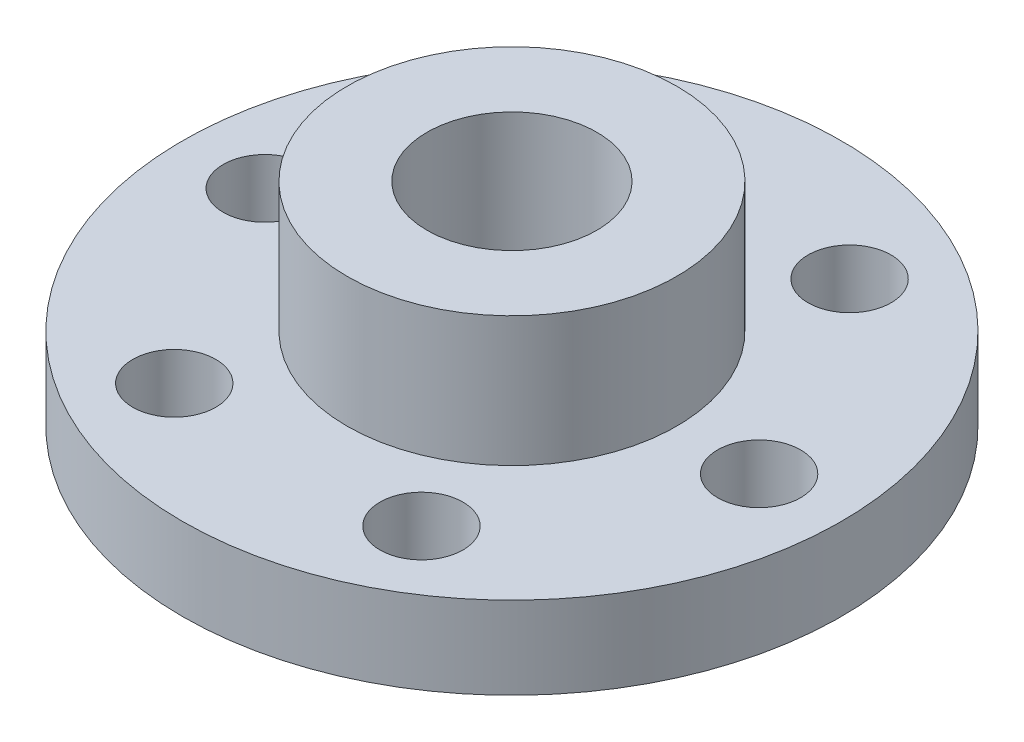
SolidWorks part; units mm, degrees
ref_plane "Front Plane" through (0, 0, 0) normal (0, 0, 1) x (1, 0, 0)
ref_plane "Top Plane" through (0, 0, 0) normal (0, 1, 0) x (1, 0, 0)
ref_plane "Right Plane" through (0, 0, 0) normal (1, 0, 0) x (0, 0, -1)
sketch "Sketch1" plane through (0, 0, 0) normal (0, 1, 0) x (1, 0, 0)
  line L0 (0, 0) -> (6.5484, 0) construction
  line L4 (0, 0) -> (-19.05, 0) construction
  circle A0 centre (0, 0) radius 4.826
  circle A1 centre (0, 0) radius 6.5484 construction
  arc A2 (3.9286, 10.8597) -> (3.9286, -10.8597) centre (0, 0) ccw construction
  circle A3 centre (0, 0) radius 25.4
  circle A5 centre (0, 0) radius 11.5484 construction
  circle A6 centre (-19.05, 0) radius 2.9766 construction
  dimension "D1" = 9.652
  dimension "D2" = 13.0969
  dimension "D3" = 23.0969
  dimension "D7" = 5.9531
  dimension "D5" = 50.8
  dimension "D4" = 19.05
extrude "Boss-Extrude1" add sketch "Sketch1" along normal blind 6.35
sketch "Sketch2" plane through (0, 6.35, 0) normal (0, 1, 0) x (1, 0, 0)
  circle A0 centre (0, 0) radius 12.7
  circle A2 centre (0, 0) radius 6.5484
  dimension "D1" = 13.0969
  dimension "D2" = 25.4
extrude "Boss-Extrude2" add sketch "Sketch2" along normal blind 10
hole_wizard "M6 Clearance Hole1" positions "Sketch3" profile "Sketch4" hole size "M6" standard "ANSI Metric" end condition through all
sketch "Sketch3" plane through (0, 6.35, 0) normal (0, 1, 0) x (1, 0, 0)
  point P0 (-19.05, 0)
  point P7 (-9.525, 16.4978)
  point P8 (9.525, 16.4978)
  point P9 (19.05, 0)
  point P10 (9.525, -16.4978)
  point P11 (-9.525, -16.4978)
  point P12 (0, 0)
  dimension "D1" = 6
sketch "Sketch4" plane through (-19.05, 6.35, 0) normal (1, 0, 0) x (0, 0, 1)
  line L0 (0, 0) -> (0, 6.35)
  line L1 (0, 6.35) -> (3.2, 6.35)
  line L2 (3.2, 6.35) -> (3.2, 0)
  line L5 (3.2, 0) -> (0, 0)
  line L11 (0, -6.35) -> (0, 107.95) construction
  dimension "Thru Hole Dia." = 6.4
  dimension "Thru Hole Depth" = 6.35
equation "\"z\" = 8\t\t\t\t'number of blades"
equation "\"de\" = 0.43in\t\t\t'entrance eye diameter"
equation "\"de_length\" = 4mm\t\t'entrance eye consistent length"
equation "\"d_exit\" = 0.18in \t\t'throat aka d1"
equation "\"d2\" = 2.1in \t\t\t'outer diameter of the impeller"
equation "\"b2\" = .2in\t\t\t'tip height from disc surface at d2; slightly higher than d_exit"
equation "\"b1\" = \"b2\" + (\"d2\"/2 - \"de\"/2)*tan(\"theta\") \t\t\t'tip height from disc surface at inlet eye"
equation "\"theta\" = 12\t\t\t'angle of blades from inner to outer "
equation "\"ae\" = 3.14*(\"de\"^2)/4\t\t'entrance eye area'"
equation "\"ce\" = 3.14*\"de\"\t\t'entrance eye circumference"
equation "\"av_ratio\" = .325\t\t'ratio of av/ae at N_s of 470, range is .275 to .375, .325 ideal. High ratio means bigger area means smaller blades"
equation "\"av\" = \"ae\"*\"av_ratio\"\t\t'area between just two blades"
equation "\"s_open\" = \"av\"/\"b1\"\t\t'width of open area"
equation "\"s\"=\"ce\" - \"z\"*\"s_open\""
equation "\"min blade thickness\" = .15in"
equation "\"bearing OD\" = 30mm"
equation "\"bearing ID\"= 10mm"
equation "\"bearing depth\"= 9mm"
equation "\"bearing outer race thickness\"= 1mm"
equation "\"bearing inner race thickness\"= 1mm"
equation "\"bearing bore\" = \"bearing depth\" + 1mm"
equation "\"lower seal OD\" = .917in\t\t'this is https://www.mcmaster.com/#9281k121/=174001b"
equation "\"lower seal ID\"= .375in"
equation "\"lower seal depth\" = .625in + .218in"
equation "\"lower seal bore\" = \"lower seal depth\" + 1mm"
equation "\"upper seal OD\" = 1.125in\t'this is https://www.mcmaster.com/#5154t33/=173zuau, needs to be visually inspected before machining!"
equation "\"upper seal ID\"= 0.625in"
equation "\"upper seal depth\"= .25in\t'aka height; these values need to be confirmed by inspection!! We may want to compress the height."
equation "\"upper seal bore\" = \"upper seal depth\" + 1mm"
equation "\"big o-ring thickness\" = .139in"
equation "\"big o-ring OD\" = 2.734in"
equation "\"big o-ring ID\" = 3.012in"
equation "\"big o-ring groove depth\" = \"big o-ring thickness\"*4/5"
equation "\"impeller center height\" = \"impeller base thickness\" + \"b1\"\t'impeller height at de"
equation "\"impeller outer height\" = \"impeller base thickness\" + \"b2\"\t'impeller height at de"
equation "\"impeller upper clearance\"= .5mm"
equation "\"impeller horizontal clearance\"= (\"d2\"*1.15 - \"d2\")/2 \t\t'clearance based on D2-D3 ratio for circular volute, ranges 1.15 to 1.2"
equation "\"impeller bottom clearance\"= .5mm"
equation "\"impeller base thickness\"= 2mm"
equation "\"impeller dowel diameter\" = 2mm"
equation "\"impeller bolt head diameter\" = \"m4 head bore diameter\""
equation "\"impeller bolt head depth\" = 4mm"
equation "\"impeller bolt stop depth\" = 3mm"
equation "\"impeller bolt bore\" = \"m4 clearance\""
equation "\"impeller shaft bore depth\" = 12mm"
equation "\"impeller shaft bore\" = 8mm"
equation "\"impeller boss depth\" = \"impeller shaft bore depth\"+\"impeller bolt stop depth\"+\"impeller bolt head depth\"-\"impeller base thickness\""
equation "\"impeller boss diameter\" = \"upper seal ID\""
equation "\"impeller dowel length\" = 2mm*2 + \"impeller shaft bore\""
equation "\"coupler motor shaft hole ID\"= 8mm"
equation "\"coupler OD\"= 17mm"
equation "\"coupler length\"= 25mm"
equation "\"motor OD\" = 64mm"
equation "\"motor shaft diameter\"= 8mm"
equation "\"motor shaft pride\"= 32mm"
equation "\"motor to bearing plate distance\" = \"motor shaft pride\" + 2mm +\"coupler length\"/2"
equation "\"square plate bolt bore\" = \"m8 clearance\""
equation "\"square plate bolt head diameter\" = 13.5mm"
equation "\"square plate bolt head depth\" = 8mm"
equation "\"square plate bolt pattern diameter\"= 3.5in"
equation "\"motor mount center bore\"= \"coupler OD\"+ 4mm"
equation "\"motor mount post radius\"= ( 3 * \"square plate bolt bore\" ) / 2"
equation "\"motor mount m4 screw hole diameter\"= 4mm"
equation "\"motor mount m4 head diameter\"= 7.25mm"
equation "\"motor mount m4 head depth\"= 4mm"
equation "\"motor mount m4 pattern diamater\" = 30mm"
equation "\"motor mount plate thickness\"= 8mm + \"motor mount m4 head depth\""
equation "\"bearing plate stop ID\" = \"bearing OD\" - 4mm"
equation "\"bearing plate stop depth\" = 3mm"
equation "\"bearing plate thickness\" = \"bearing bore\" + \"bearing plate stop depth\" + \"shaft bearing stop length\""
equation "\"lower seal plate lip depth\" = 2mm"
equation "\"lower seal plate lip ID\" = \"lower seal OD\" - 3mm"
equation "\"lower seal plate thickness\" = \"lower seal plate lip depth\" + \"lower seal bore\""
equation "\"shaft coupler section diameter\" = 8mm"
equation "\"shaft coupler section length\" = \"motor to bearing plate distance\" - \"motor shaft pride\" - 2mm"
equation "\"shaft bearing section diameter\" = \"bearing ID\""
equation "\"shaft bearing section length\" = \"bearing plate stop depth\" + \"bearing depth\""
equation "\"shaft bearing stop diameter\" = \"bearing ID\" + 4mm"
equation "\"shaft bearing stop length\" = 3mm"
equation "\"shaft lower seal section diameter\" = \"lower seal ID\""
equation "\"shaft lower seal section length\" = \"lower seal plate thickness\" + 1mm"
equation "\"shaft impeller section diameter\" = \"impeller shaft bore\""
equation "\"shaft impeller section length\" = \"upper seal plate thickness\" + \"upper seal plate riser\" + \"impeller bottom clearance\" + \"impeller base thickness\" - \"impeller bolt head depth\" - \"impeller bolt stop depth\""
equation "\"upper seal plate thickness\" = \"upper seal plate pressure hole diameter\"+10mm"
equation "\"upper seal plate lip ID\" = \"upper seal OD\" - 3mm"
equation "\"upper seal plate riser\" = 6.59mm \t\t'this number needs to be read from the housing file"
equation "\"upper seal plate pressure hole diameter\" = .125in\t'this is 1/8 drill "
equation "\"upper seal plate pressure tap diameter\" = .328125in \t'this is 21/64 drill for a 1/8 ANPT tap"
equation "\"upper seal plate pressure tap grip\" = 5mm\t\t'this is the area around the tap so it doesn't crack"
equation "\"upper seal plate pressure tap depth\" = 12mm"
equation "\"impeller cavity center height\"= \"impeller bottom clearance\" + \"impeller upper clearance\" + \"impeller center height\""
equation "\"impeller cavity diameter\"= 2 * \"impeller horizontal clearance\" + \"d2\" \t\t\t\t\t\t\t\t\t'called D3 analytically"
equation "\"impeller cavity outer height\"= \"impeller bottom clearance\" + \"impeller upper clearance\" + \"impeller base thickness\" + \"b2\" \t\t'this is height at impeller diameter d2, not at d3"
equation "\"impeller housing thickness\"= \"impeller housing exit threaded diameter\" + 2*\"impeller housing outlet grip\""
equation "\"impeller housing diameter\" = 4.5in"
equation "\"impeller housing bolt count\" = 8"
equation "\"impeller housing bolt diameter\" = \"m6 clearance\""
equation "\"impeller housing bolt pattern diameter\" = 3.5in"
equation "\"impeller housing threaded inlet diameter\" = 0.71875in \t'this is the 23/32 drill size for 1/2 NPT fitting https://www.mcmaster.com/#50715k269/=176pljy"
equation "\"impeller housing threaded inlet depth\"= .6in"
equation "\"impeller housing exit threaded diameter\"= 0.515625in \t\t'this is the 33/64 drill size for 9/16-18 fitting, expecting swagelok SS-8FK0-1-6STH fitting"
equation "\"impeller housing exit threaded depth\"= 10mm"
equation "\"impeller housing diffuser conical angle\"=10"
equation "\"impeller housing diffuser tangent angle\"=5"
equation "\"impeller housing diffuser final diameter\" = .38in\t\t'aka d2'"
equation "\"impeller housing outlet grip\" = 5mm"
equation "\"end mill size\" = 0.375in\t'for 3/8 endmill"
equation "\"m4 clearance\" = 0.171875in \t'this is 11/64 bit for 4.36mm"
equation "\"m4 tap\" = 0.125in\t\t'this is 1/8 bit for 3.17mm"
equation "\"m4 head bore diameter\" = 7.5mm"
equation "\"m4 head bore depth\" = 5mm\t'actual is ~4mm"
equation "\"m6 clearance\" = 0.234375in\t'this is 15/64 bit = 5.95mm, could use 6mm bit, B bit for 6.04mm or 1/4 bit for 6.35mm"
equation "\"m6 tap\" = 5mm\t\t\t'5mm is appropriate, could use 13/64 or #5,6,7"
equation "\"m6 head bore diameter\" = 11mm\t\t"
equation "\"m6 head bore depth\" = 7mm\t'actual is 6mm"
equation "\"m8 clearance\" = 0.3125in\t'this is 5/16in for 7.93mm, could use 8mm, O,P, or 21/64"
equation "\"m8 tap\" = 0.265625in\t\t'this is 17/64 for 6.746875mm"
equation "\"m8 head bore diameter\" = 14mm"
equation "\"m8 head bore depth\" = 9mm\t'actual is 8mm"
equation "\"D1@Sketch1\"=\"impeller housing diffuser final diameter\""
equation "\"D2@Sketch1\"=\"impeller housing exit threaded diameter\""
equation "\"D3@Sketch1\"=\"impeller housing exit threaded diameter\"+\"impeller housing outlet grip\"*2 "
equation "\"D7@Sketch1\"=\"m6 clearance\""
equation "\"D1@Sketch2\"=\"impeller housing exit threaded diameter\""
equation "\"D1@Boss-Extrude2\"=10mm"
equation "\"diffuser cartridge OD\" =.75in"
equation "\"diffuser flange bolt pattern diameter\" = 1.4in"
equation "\"D4@Sketch1\"=.75in"
